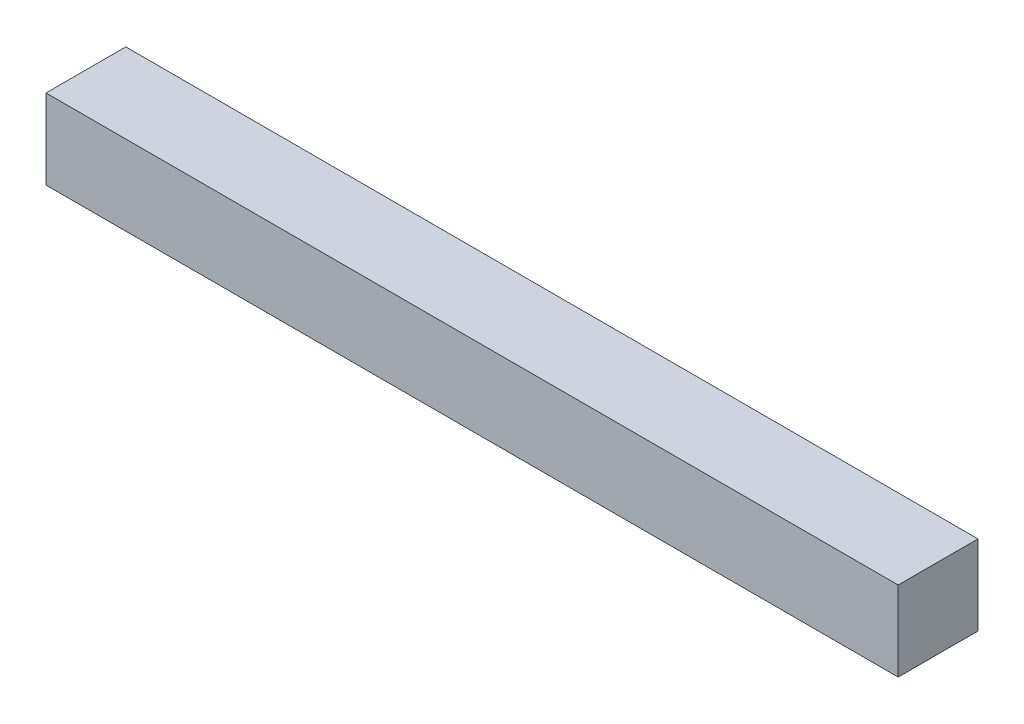
SolidWorks part; units mm, degrees
ref_plane "Front Plane" through (0, 0, 0) normal (0, 0, 1) x (1, 0, 0)
ref_plane "Top Plane" through (0, 0, 0) normal (0, 1, 0) x (1, 0, 0)
ref_plane "Right Plane" through (0, 0, 0) normal (1, 0, 0) x (0, 0, -1)
sketch "Sketch1" plane through (0, 0, 0) normal (0, 0, 1) x (1, 0, 0)
  line L1 (0, 0) -> (106.79, 0)
  line L2 (0, 0) -> (0, -10)
  line L3 (0, -10) -> (106.79, -10)
  line L4 (106.79, 0) -> (106.79, -10)
  line L5 (0, 0) -> (106.79, -10) construction
  line L6 (0, -10) -> (106.79, 0) construction
  point P4 (53.395, -5)
  dimension "D1" = 10
  dimension "D2" = 106.79
extrude "Boss-Extrude1" add sketch "Sketch1" along normal blind 10
